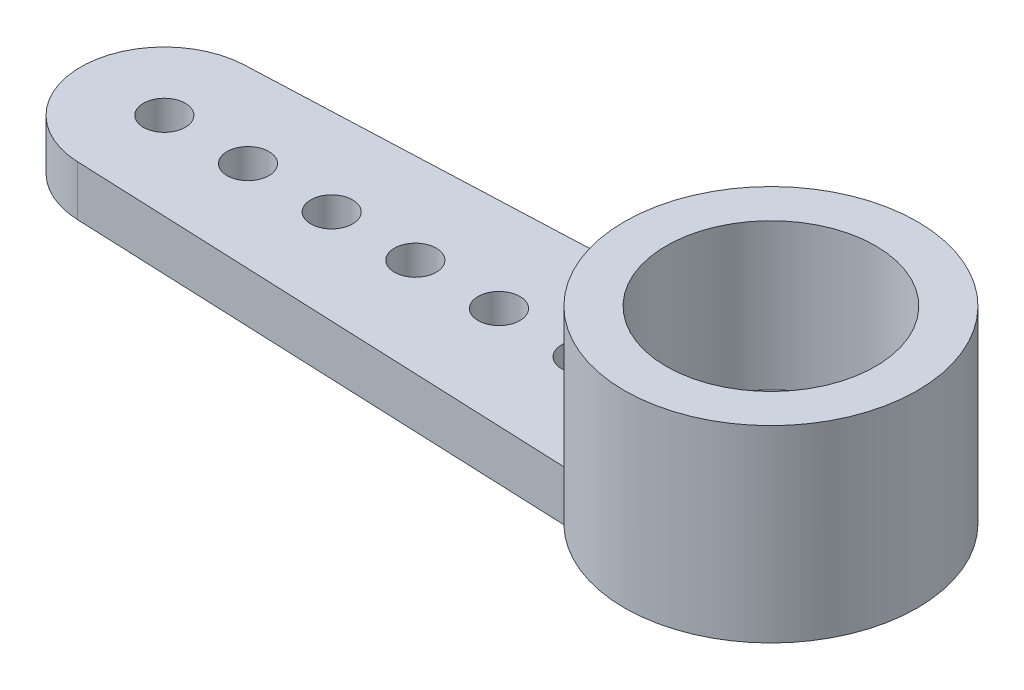
SolidWorks part; units mm, degrees
ref_plane "前视基准面" through (0, 0, 0) normal (0, 0, 1) x (1, 0, 0)
ref_plane "上视基准面" through (0, 0, 0) normal (0, 1, 0) x (1, 0, 0)
ref_plane "右视基准面" through (0, 0, 0) normal (1, 0, 0) x (0, 0, -1)
sketch "草图1" plane through (0, 0, 0) normal (0, 1, 0) x (1, 0, 0)
  line L0 (-21.7997, 0) -> (21.9881, 0) construction
  line L1 (-7.4524, 1.9983) -> (4.6826, 2.5016)
  line L2 (-7.4524, -1.9983) -> (4.6826, -2.5016)
  circle A0 centre (7.1304, 0) radius 3.5
  circle A1 centre (7.1304, 0) radius 2.5
  arc A2 (-7.4524, 1.9983) -> (-7.4524, -1.9983) centre (-7.3696, 0) ccw
  circle A3 centre (-7.3696, 0) radius 0.5
  circle A4 centre (-5.3696, 0) radius 0.5
  circle A5 centre (-3.3696, 0) radius 0.5
  circle A6 centre (-1.3696, 0) radius 0.5
  circle A7 centre (0.6304, 0) radius 0.5
  circle A8 centre (2.6304, 0) radius 0.5
  point P7 (-7.3696, 0)
  point P10 (2.6304, 0)
  dimension "D1" = 7
  dimension "D2" = 5
  dimension "D4" = 4
  dimension "D6" = 1
  dimension "D3" = 14.5
  dimension "D5" = 10
  dimension "D8" = 4.75
  dimension "D7" = 6
extrude "凸台-拉伸1" add sketch "草图1" along normal blind 1.2 contours L0 A2 L2 A0 A8 A7 A6 A5 A4 A3 | A2 L0 A3 A4 A5 A6 A7 A8 A0 L1 region at (-2.2357, 0, -1.1913) region at (-2.2357, 0, 1.1913)
extrude "凸台-拉伸2" add sketch "草图1<3>" along normal blind 4.5 contours A0 | A1
sketch "草图1<3>" plane through (0, 0, 0) normal (0, 1, 0) x (1, 0, 0) same geometry as "草图1"
sketch "草图3" plane through (0, 0, 0) normal (0, 1, 0) x (1, 0, 0)
  circle A0 centre (7.1304, 0) radius 1.25
  circle A1 centre (7.1304, 0) radius 2.5 construction
  circle A2 centre (7.1304, 0) radius 2.5
  dimension "D1" = 2.5
extrude "凸台-拉伸3" add sketch "草图1<4>" along normal blind 1 contours A1
sketch "草图1<4>" plane through (0, 0, 0) normal (0, 1, 0) x (1, 0, 0) same geometry as "草图1"
extrude "切除-拉伸1" cut sketch "草图3" along normal blind 1 contours A0
